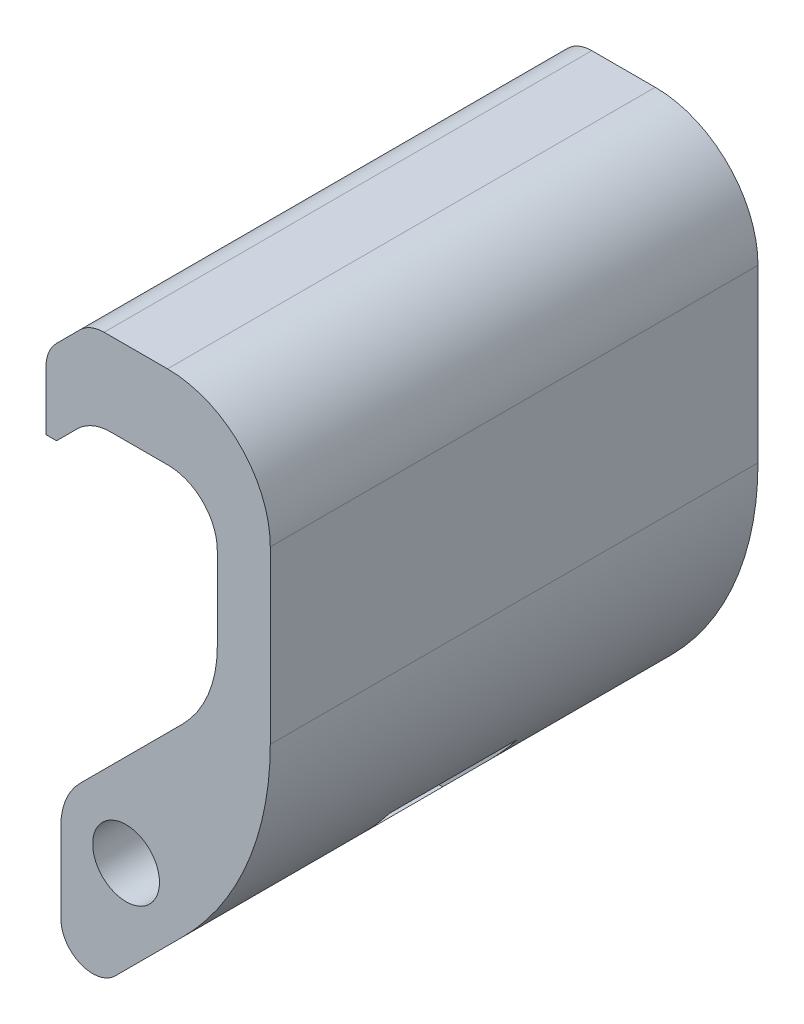
SolidWorks part; units mm, degrees
ref_plane "Front" through (0, 0, 0) normal (0, 0, 1) x (1, 0, 0)
ref_plane "Top" through (0, 0, 0) normal (0, 1, 0) x (1, 0, 0)
ref_plane "Right" through (0, 0, 0) normal (1, 0, 0) x (0, 0, -1)
sketch "Sketch1" plane through (0, 0, 0) normal (0, 0, 1) x (1, 0, 0)
  line L6 (-1.575, 0) -> (-3.075, 0) construction
  line L10 (-3.7768, 18.386) -> (-3.7768, 15.6126)
  line L16 (-3.7768, 15.6126) -> (-3.2768, 15.6126)
  line L17 (-3.2768, 15.6126) -> (-2.295, 16.5945)
  line L23 (-3.2768, 19.5931) -> (-2.1778, 20.6922)
  line L24 (-1.0357, 21.1652) -> (1.9535, 21.1652)
  line L25 (6.8, 16.3187) -> (6.8, 8.2503)
  line L26 (-0.7202, 17.2468) -> (1.9795, 17.2468)
  line L27 (4.3, 14.9263) -> (4.3, 10.9803)
  line L28 (2.6513, 7) -> (-2.1744, 2.1744)
  line L30 (-3.075, 0) -> (-3.075, -3.8024)
  line L31 (-0.5143, -4.863) -> (2.6995, -1.6492)
  circle A0 centre (0, 0) radius 1.575
  circle A3 centre (0, 0) radius 3.075 construction
  arc A22 (-3.7768, 18.386) -> (-3.2768, 19.5931) centre (-2.0697, 18.386) cw
  arc A23 (-2.1778, 20.6922) -> (-1.0357, 21.1652) centre (-1.0357, 19.5501) cw
  arc A24 (1.9535, 21.1652) -> (6.8, 16.3187) centre (1.9535, 16.3187) cw
  arc A25 (-2.295, 16.5945) -> (-0.7202, 17.2468) centre (-0.7202, 15.0197) cw
  arc A26 (1.9795, 17.2468) -> (4.3, 14.9263) centre (1.9795, 14.9263) cw
  arc A27 (4.3, 10.9803) -> (2.6513, 7) centre (-1.329, 10.9803) cw
  arc A28 (-2.1744, 2.1744) -> (-3.075, 0) centre (0, 0) ccw
  arc A29 (2.6995, -1.6492) -> (6.8, 8.2503) centre (-7.2, 8.2503) ccw
  arc A30 (-3.075, -3.8024) -> (-0.5143, -4.863) centre (-1.575, -3.8024) ccw
  point P32 (3.3047, 7.6166)
  point P33 (3.075, -1.199)
  point P34 (2.5789, -1.6495)
  point P35 (-1.1734, -5.5222)
  point P36 (-3.75, 15.6126)
  point P38 (-1.8393, 16.7832)
  point P40 (-3.2768, 19.5501)
  dimension "D1" = 3.15
  dimension "D7" = 14
  dimension "D8" = 1.5
  dimension "D2" = 1.5
  dimension "D4" = 45
  dimension "D5" = 0.5
  dimension "D3" = 2.5
  dimension "D6" = 45
  dimension "D9" = 4.3
  dimension "D10" = 7
extrude "Boss-Extrude1" add sketch "Sketch1" along normal mid plane 23
sketch "Sketch2" plane through (0, 0, 0) normal (0, 0, 1) x (1, 0, 0)
  circle A0 centre (0, 0) radius 3.9286
extrude "Cut-Extrude1" cut sketch "Sketch2" against normal mid plane 6
equation "\"D1@Sketch1\"=\"Hardware Clearance Hole Diameter@Box Assy.Assembly\""
